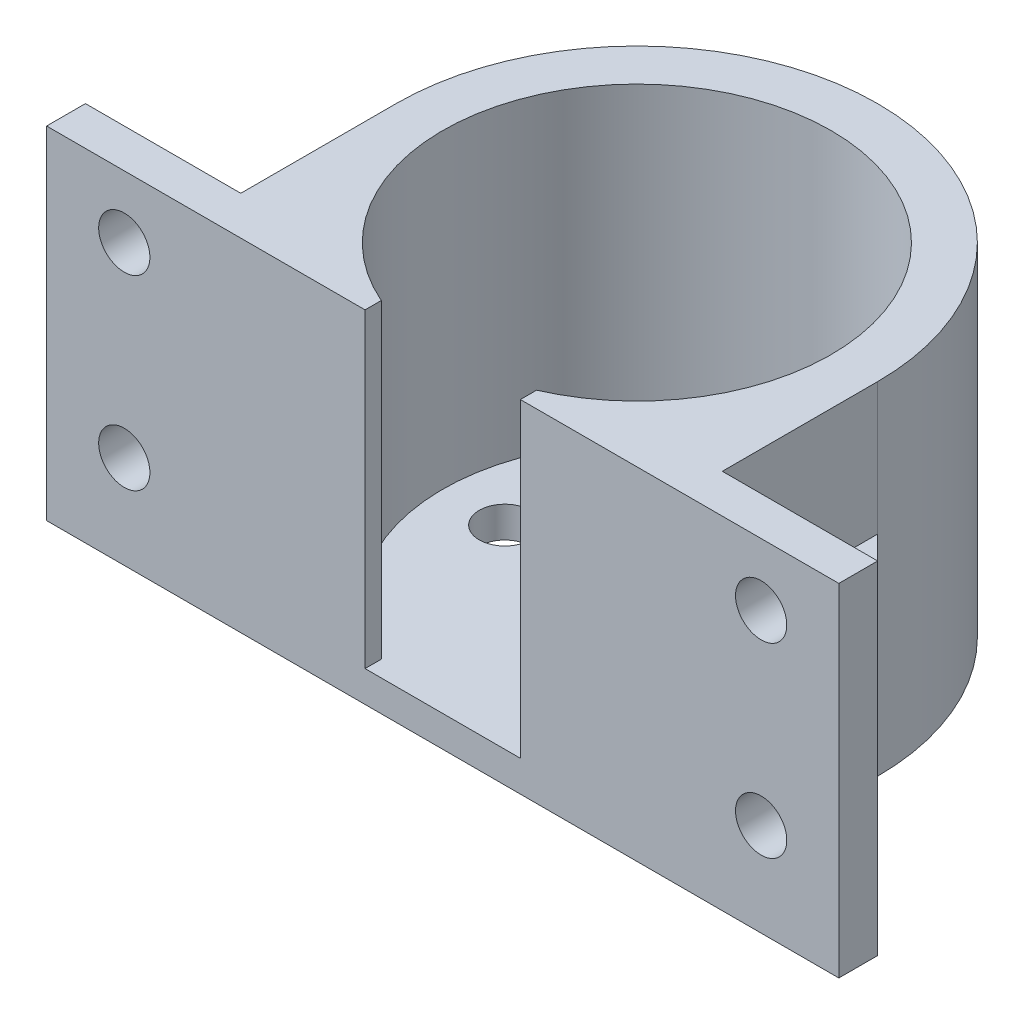
SolidWorks part; units mm, degrees
ref_plane "Front Plane" through (0, 0, 0) normal (0, 0, 1) x (1, 0, 0)
ref_plane "Top Plane" through (0, 0, 0) normal (0, 1, 0) x (1, 0, 0)
ref_plane "Right Plane" through (0, 0, 0) normal (1, 0, 0) x (0, 0, -1)
sketch "Sketch1" plane through (0, 0, 0) normal (0, 1, 0) x (1, 0, 0)
  line L0 (-25.5, -12.5) -> (-5, -12.5)
  line L1 (25.5, -12.5) -> (25.5, -10)
  line L2 (25.5, -10) -> (15.5, -10)
  line L3 (-25.5, -10) -> (-25.5, -12.5)
  line L4 (15.5, 0) -> (15.5, -10)
  line L5 (-15.5, 0) -> (-15.5, -10)
  line L6 (-15.5, -10) -> (-25.5, -10)
  line L7 (-5, -11.4564) -> (-5, -12.5)
  line L8 (5, -11.4564) -> (5, -12.5)
  line L9 (5, -12.5) -> (25.5, -12.5)
  line L10 (-5, -12.5) -> (5, -12.5)
  line L11 (-8.5, 0) -> (8.5, 0) construction
  arc A0 (5, -11.4564) -> (-5, -11.4564) centre (0, 0) ccw
  arc A1 (15.5, 0) -> (-15.5, 0) centre (0, 0) ccw
  circle A2 centre (-8.5, 0) radius 1.65
  circle A3 centre (8.5, 0) radius 1.65
  circle A4 centre (0, 0) radius 4.5
  point P7 (0, -12.5)
  point P18 (0, 0)
  dimension "D1" = 3
  dimension "D2" = 25
  dimension "D7" = 3.3
  dimension "D8" = 9
  dimension "D3" = 2.5
  dimension "D4" = 10
  dimension "D5" = 10
  dimension "D6" = 17
extrude "Boss-Extrude1" add sketch "Sketch1" along normal blind 20 contours L4 A1 L5 L6 L3 L0 L7 A0 L8 L9 L1 L2 region at (-24.9182, 0, 11.25)
ref_plane "Plane1" through (0, 10, 0) normal (0, 1, 0) x (1, 0, 0)
sketch "Sketch3" plane through (0, 10, 0) normal (0, 1, 0) x (1, 0, 0)
  line L0 (15.5, 0) -> (25.5, -10)
rib "Rib1" sketch "Sketch3" sketch "Sketch3" thickness 3 extrusion direction parallel to sketch draft on no parameters "D1"=3
mirror "Mirror1" about plane through (0, 0, 0) normal (1, 0, 0) of "Rib1"
sketch "Sketch4" plane through (0, 0, 0) normal (0, 0, 1) x (1, 0, 0)
  line L0 (20.5, 20) -> (20.5, 0) construction
  line L8 (20.5, 16) -> (20.5, 4) construction
  circle A0 centre (20.5, 16) radius 1.65
  circle A1 centre (20.5, 4) radius 1.65
  point P9 (20.5, 10)
  dimension "D1" = 3.3
  dimension "D2" = 12
  dimension "D3" = 20.5
extrude "Cut-Extrude2" cut sketch "Sketch4" along normal blind 18
mirror "Mirror2" about plane through (0, 0, 0) normal (1, 0, 0) of "Cut-Extrude2"
extrude "Boss-Extrude2" add sketch "Sketch1<4>" against normal blind 2 contours L8 A0 L7 L10 A2 A3 | L4 A1 L5 L6 L3 L0 L7 A0 L8 L9 L1 L2 region at (-24.9182, 0, 11.25) region at (-4.6464, 0, 11.9782)
sketch "Sketch1<4>" plane through (0, 0, 0) normal (0, 1, 0) x (1, 0, 0) same geometry as "Sketch1"
